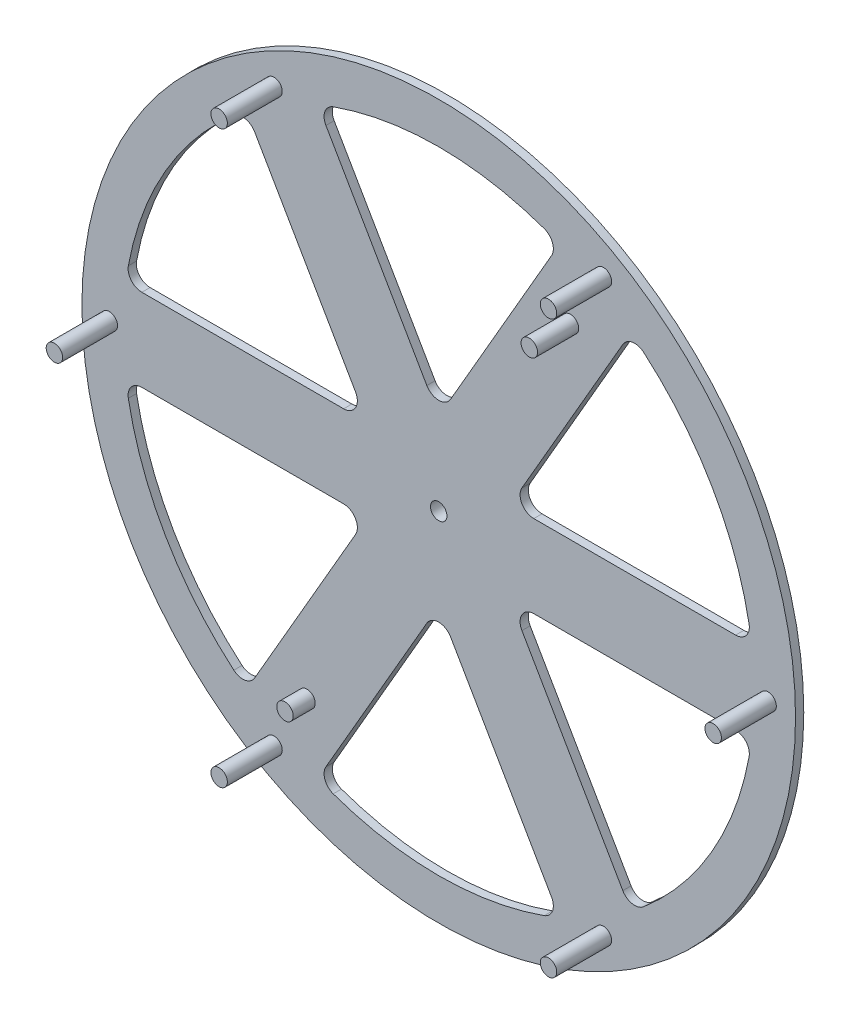
SolidWorks part; units mm, degrees
ref_plane "前视基准面" through (0, 0, 0) normal (0, 0, 1) x (1, 0, 0)
ref_plane "上视基准面" through (0, 0, 0) normal (0, 1, 0) x (1, 0, 0)
ref_plane "右视基准面" through (0, 0, 0) normal (1, 0, 0) x (0, 0, -1)
other "Configuration Table"
sketch "草图1" plane through (0, 0, 0) normal (0, 0, 1) x (1, 0, 0)
  circle A0 centre (0, 0) radius 130
  point P0 (0, 0)
  point P19 (0, 0)
  dimension "D1" = 260
extrude "凸台-拉伸1" add sketch "草图1" against normal blind 3 contours A0 region at (0, 0, 0)
sketch "草图2" plane through (0, 0, 0) normal (0, 0, 1) x (1, 0, 0)
  line L0 (0, 0) -> (-120, 0) construction
  circle A0 centre (0, 0) radius 3
  circle A1 centre (-120, 0) radius 3
  circle A2 centre (-60, 103.923) radius 3
  circle A3 centre (60, 103.923) radius 3
  circle A4 centre (120, 0) radius 3
  circle A5 centre (60, -103.923) radius 3
  circle A6 centre (-60, -103.923) radius 3
  point P17 (0, 0)
  dimension "D1" = 6
  dimension "D2" = 120
  dimension "D3" = 6
extrude "凸台-拉伸2" add sketch "草图2" along normal blind 20 contours A1 | A3 | A2 | A4 | A5 | A6 region at (-120, 0, 0) region at (60, 103.923, 0)
sketch "草图3" plane through (0, 0, 0) normal (0, 0, 1) x (1, 0, 0)
  circle A0 centre (0, 0) radius 3
  dimension "D1" = 6
sketch "草图4" plane through (0, 0, 0) normal (0, 0, 1) x (1, 0, 0)
  line L0 (-25.9808, -15) -> (-69.9992, -91.2421) construction
  line L1 (0, 0) -> (-60, -103.923) construction
  line L2 (0, 0) -> (-130, 0) construction
  line L3 (0, 0) -> (-65, -112.5833) construction
  line L4 (-30.3109, -22.5) -> (-67.0737, -86.175)
  line L5 (-34.641, -15) -> (-108.1665, -15)
  line L6 (-25.9808, -15) -> (-114.0175, -15) construction
  line L7 (-34.641, 15) -> (-108.1665, 15)
  line L8 (-30.3109, 22.5) -> (-67.0737, 86.175)
  line L9 (-4.3301, 37.5) -> (-41.0929, 101.175)
  line L10 (4.3301, 37.5) -> (41.0929, 101.175)
  line L11 (30.3109, 22.5) -> (67.0737, 86.175)
  line L12 (34.641, 15) -> (108.1665, 15)
  line L13 (34.641, -15) -> (108.1665, -15)
  line L14 (30.3109, -22.5) -> (67.0737, -86.175)
  line L15 (4.3301, -37.5) -> (41.0929, -101.175)
  line L16 (-4.3301, -37.5) -> (-41.0929, -101.175)
  circle A0 centre (0, 0) radius 130 construction
  arc A1 (-130, 0) -> (-65, -112.5833) centre (0, 0) ccw construction
  arc A2 (-113.0832, -20.9091) -> (-74.6494, -87.4784) centre (0, 0) ccw
  arc A3 (-30.3109, -22.5) -> (-34.641, -15) centre (-34.641, -20) ccw
  arc A4 (-114.0175, -15) -> (-69.9992, -91.2421) centre (0, 0) ccw construction
  arc A5 (-74.6494, -87.4784) -> (-67.0737, -86.175) centre (-71.4038, -83.675) ccw
  arc A6 (-113.0832, -20.9091) -> (-108.1665, -15) centre (-108.1665, -20) cw
  arc A7 (-74.6494, 87.4784) -> (-113.0832, 20.9091) centre (0, 0) ccw
  arc A8 (-74.6494, 87.4784) -> (-67.0737, 86.175) centre (-71.4038, 83.675) cw
  arc A9 (-113.0832, 20.9091) -> (-108.1665, 15) centre (-108.1665, 20) ccw
  arc A10 (-34.641, 15) -> (-30.3109, 22.5) centre (-34.641, 20) ccw
  arc A11 (38.4338, 108.3875) -> (-38.4338, 108.3875) centre (0, 0) ccw
  arc A12 (38.4338, 108.3875) -> (41.0929, 101.175) centre (36.7628, 103.675) cw
  arc A13 (-38.4338, 108.3875) -> (-41.0929, 101.175) centre (-36.7628, 103.675) ccw
  arc A14 (-4.3301, 37.5) -> (4.3301, 37.5) centre (0, 40) ccw
  arc A15 (113.0832, 20.9091) -> (74.6494, 87.4784) centre (0, 0) ccw
  arc A16 (113.0832, 20.9091) -> (108.1665, 15) centre (108.1665, 20) cw
  arc A17 (74.6494, 87.4784) -> (67.0737, 86.175) centre (71.4038, 83.675) ccw
  arc A18 (30.3109, 22.5) -> (34.641, 15) centre (34.641, 20) ccw
  arc A19 (74.6494, -87.4784) -> (113.0832, -20.9091) centre (0, 0) ccw
  arc A20 (74.6494, -87.4784) -> (67.0737, -86.175) centre (71.4038, -83.675) cw
  arc A21 (113.0832, -20.9091) -> (108.1665, -15) centre (108.1665, -20) ccw
  arc A22 (34.641, -15) -> (30.3109, -22.5) centre (34.641, -20) ccw
  arc A23 (-38.4338, -108.3875) -> (38.4338, -108.3875) centre (0, 0) ccw
  arc A24 (-38.4338, -108.3875) -> (-41.0929, -101.175) centre (-36.7628, -103.675) cw
  arc A25 (38.4338, -108.3875) -> (41.0929, -101.175) centre (36.7628, -103.675) ccw
  arc A26 (4.3301, -37.5) -> (-4.3301, -37.5) centre (0, -40) ccw
  point P71 (0, 0)
  dimension "D2" = 5
  dimension "D1" = 15
  dimension "D3" = 6
extrude "切除-拉伸1" cut sketch "草图4" against normal up to next (3 mm away)
sketch "草图5" plane through (0, 0, 0) normal (0, 0, 1) x (1, 0, 0)
  line L0 (0, 0) -> (-60, -103.923) construction
  circle A0 centre (-48, -83.1384) radius 3
  point P11 (0, 0)
  dimension "D1" = 6
  dimension "D2" = 24
extrude "凸台-拉伸4" add sketch "草图5" along normal blind 8
sketch "草图6" plane through (0, 0, 0) normal (0, 0, 1) x (1, 0, 0)
  line L0 (0, 0) -> (60, 103.923) construction
  circle A0 centre (48, 83.1384) radius 3
  dimension "D1" = 6
  dimension "D2" = 24
extrude "凸台-拉伸5" add sketch "草图6" along normal blind 15
extrude "切除-拉伸2" cut sketch "草图3" against normal up to next (3 mm away)
sketch "草图7" plane through (0, 0, -3) normal (0, 0, -1) x (-1, 0, 0)
  circle A0 centre (0, 0) radius 6
  dimension "D1" = 12
extrude "拉伸-薄壁1" add sketch "草图7" along normal blind 2 thin thin type one direction reverse wall 3
